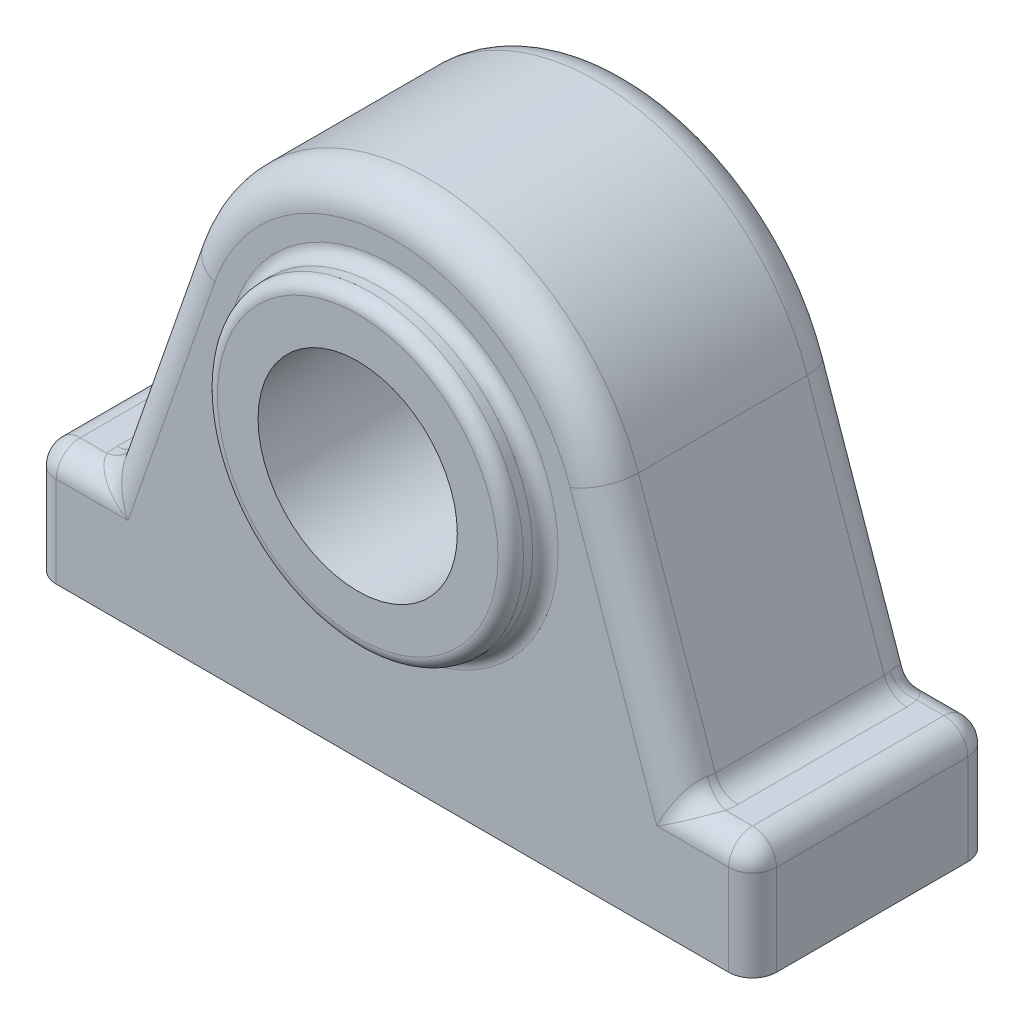
SolidWorks part; units mm, degrees
note: The reader was unsure of these and kept them because the rebuilt part matched: shared geometry of "Sketch1<4>".
ref_plane "Front Plane" through (0, 0, 0) normal (0, 0, 1) x (1, 0, 0)
ref_plane "Top Plane" through (0, 0, 0) normal (0, 1, 0) x (1, 0, 0)
ref_plane "Right Plane" through (0, 0, 0) normal (1, 0, 0) x (0, 0, -1)
sketch "Sketch1" plane through (0, 0, 0) normal (0, 0, 1) x (1, 0, 0)
  line L0 (0, 0) -> (0, 315) construction
  line L1 (225.9, 0) -> (-225.9, 0)
  line L2 (-225.9, 0) -> (-225.9, 72)
  line L3 (-225.9, 72) -> (-184, 72)
  line L4 (-184, 72) -> (-132.2442, 220.9508)
  line L5 (184, 72) -> (132.2442, 220.9508)
  line L6 (225.9, 72) -> (184, 72)
  line L7 (225.9, 0) -> (225.9, 72)
  arc A0 (-132.2442, 220.9508) -> (132.2442, 220.9508) centre (0, 175) cw
  circle A1 centre (0, 175) radius 96
  circle A2 centre (0, 175) radius 62.5
  dimension "D4" = 140
  dimension "D6" = 192
  dimension "D7" = 125
  dimension "D1" = 451.8
  dimension "D2" = 72
  dimension "D3" = 368
  dimension "D5" = 175
extrude "Boss-Extrude1" add sketch "Sketch1" along normal mid plane 150 contours L0 L1 L7 L6 L5 A0 A1 | L1 L0 A1 A0 L4 L3 L2
extrude "Boss-Extrude2" add sketch "Sketch1<4>" along normal mid plane 193.6 contours A1 L0 A2 | L0 A1 A2
sketch "Sketch1<4>" plane through (0, 0, 0) normal (0, 0, 1) x (1, 0, 0) same geometry as "Sketch1"
fillet "Fillet2" radius 8 4 edges at (96, 175, -96.8) (96, 175, -75) (96, 175, 75) (96, 175, 96.8)
fillet "Fillet3" radius 22 6 edges at (-158.1221, 146.4754, -75) (-158.1221, 146.4754, 75) (158.1221, 146.4754, -75) (158.1221, 146.4754, 75) (0, 315, -75) (0, 315, 75)
fillet "Fillet5" radius 15 4 edges at (-193.3049, 72, -75) (-193.3049, 72, 75) (193.3049, 72, -75) (193.3049, 72, 75)
fillet "Fillet6" radius 15 20 edges at (-225.9, 28.5, 75) (-225.9, 67.6066, 70.6066) (-225.9, 28.5, -75) (-225.9, 67.6066, -70.6066) (-177.56, 68.8447, 69.2035) (-183.6954, 72, 56.5464) (-177.56, 68.8447, -69.2035) (-183.6954, 72, -56.5464) (225.9, 28.5, 75) (225.9, 67.6066, 70.6066) (225.9, 28.5, -75) (225.9, 67.6066, -70.6066) (177.56, 68.8447, 69.2035) (183.6954, 72, 56.5464) (177.56, 68.8447, -69.2035) (183.6954, 72, -56.5464) (-225.9, 72, 0) (-184, 72, 0) (225.9, 72, 0) (184, 72, 0)
